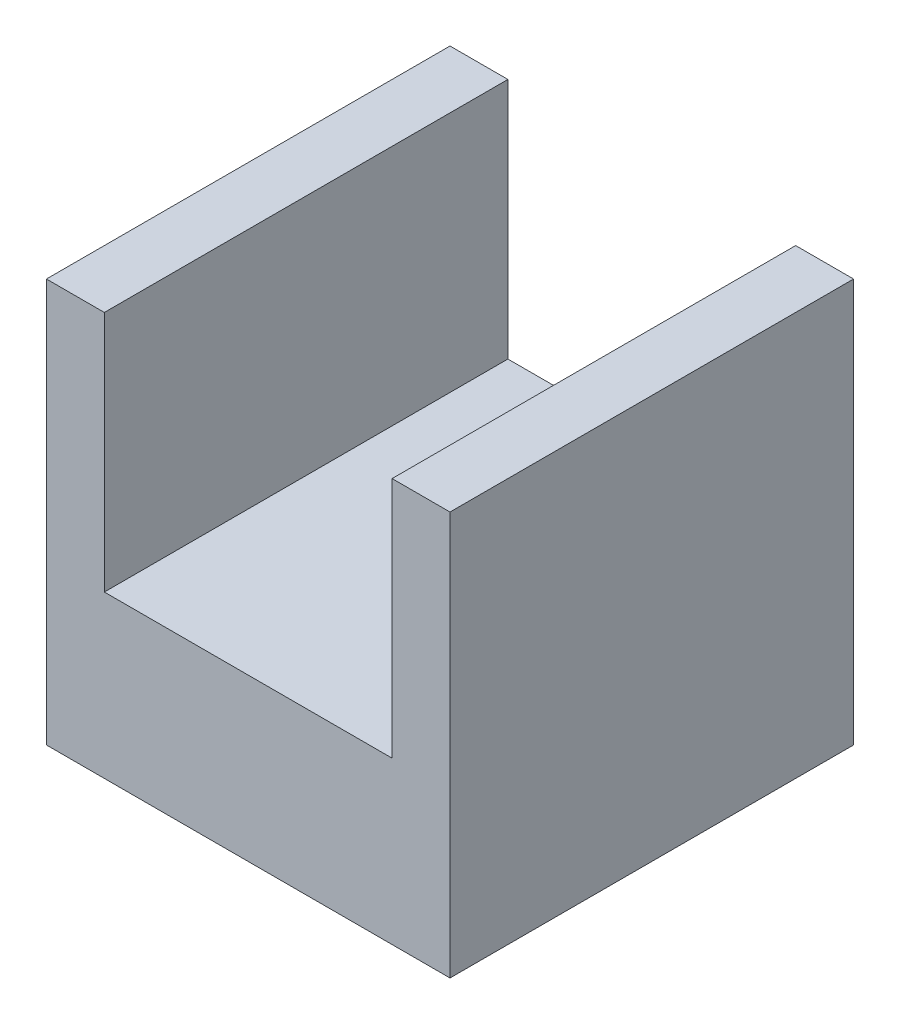
SolidWorks part; units mm, degrees
ref_plane "Front Plane" through (0, 0, 0) normal (0, 0, 1) x (1, 0, 0)
ref_plane "Top Plane" through (0, 0, 0) normal (0, 1, 0) x (1, 0, 0)
ref_plane "Right Plane" through (0, 0, 0) normal (1, 0, 0) x (0, 0, -1)
sketch "Sketch1" plane through (0, 0, 0) normal (0, 0, 1) x (1, 0, 0)
  line L1 (-20, 20) -> (20, 20)
  line L2 (-20, 20) -> (-20, -20)
  line L3 (-20, -20) -> (20, -20)
  line L4 (20, 20) -> (20, -20)
  line L5 (-20, 20) -> (20, -20) construction
  line L6 (-20, -20) -> (20, 20) construction
  point P0 (0, 0)
  dimension "D1" = 40
extrude "Boss-Extrude1" add sketch "Sketch1" along normal blind 40 contours L2 L1 L4 L3
sketch "Sketch2" plane through (0, 0, 0) normal (0, 0, 1) x (1, 0, 0)
  line L5 (14.26, 20) -> (14.26, -4)
  line L6 (14.26, -4) -> (-14.26, -4)
  line L7 (-20, 20) -> (20, 20) construction
  line L8 (20, 20) -> (20, -20) construction
  line L9 (0, -22) -> (0, 22) construction
  line L10 (-14.26, 20) -> (-14.26, -4)
  line L11 (-14.26, 20) -> (14.26, 20)
  point P19 (0, -4)
  dimension "D1" = 24
  dimension "D2" = 5.74
extrude "Cut-Extrude1" cut sketch "Sketch2" along normal up to next
ref_plane "Plane1" through (0, 0, 20) normal (0, 0, 1) x (1, 0, 0)
ref_axis "Axis1" through (0, 22, 20) along (0, -1, 0)
